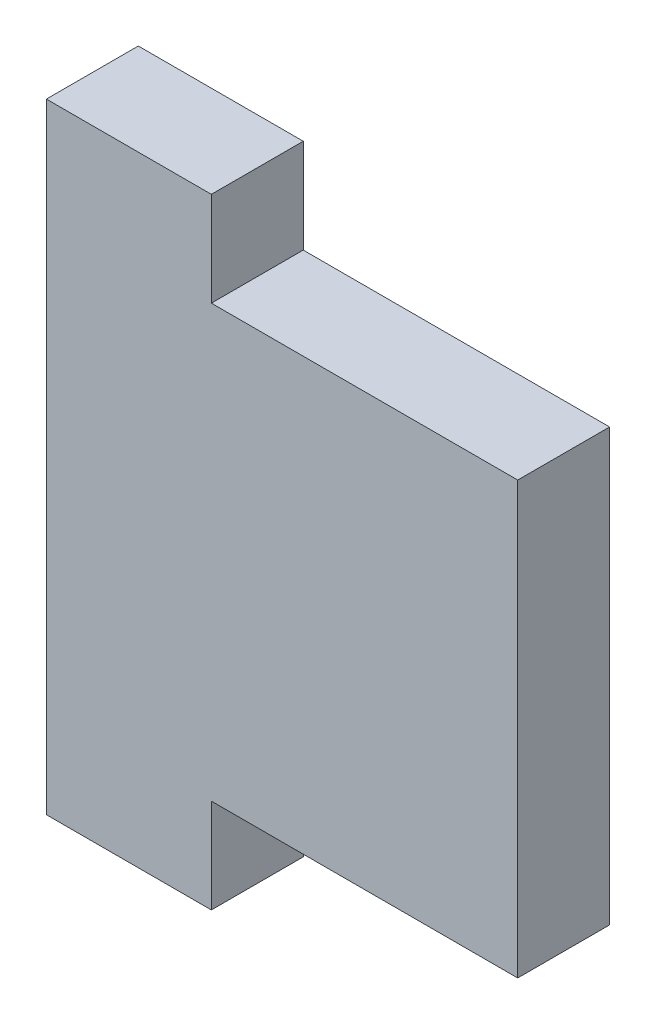
SolidWorks part; units mm, degrees
ref_plane "Front" through (0, 0, 0) normal (0, 0, 1) x (1, 0, 0)
ref_plane "Top" through (0, 0, 0) normal (0, 1, 0) x (1, 0, 0)
ref_plane "Right" through (0, 0, 0) normal (1, 0, 0) x (0, 0, -1)
ref_axis "side-side" through (80.9, 0, 0) along (-1, 0, 0)
ref_axis "up-down" through (0, 50, 0) along (0, -1, 0)
ref_axis "front-back" through (0, 0, -80.9) along (0, 0, 1)
sketch "Sketch1" plane through (0, 0, 0) normal (0, 0, 1) x (1, 0, 0)
  line L0 (-50.038, -11.6205) -> (-84.9201, -11.6205) construction
  line L1 (-54.483, 11.6205) -> (-70.993, 11.6205)
  line L2 (-54.483, 11.6205) -> (-54.483, -11.6205)
  line L3 (-54.483, -11.6205) -> (-70.993, -11.6205)
  line L4 (-79.883, 16.7005) -> (-79.883, -16.7005)
  line L5 (-50.038, 11.6205) -> (-84.9201, 11.6205) construction
  line L6 (-54.483, -11.6205) -> (-54.483, 11.6205) construction
  line L7 (-70.993, -11.6205) -> (-70.993, -16.7005)
  line L8 (-70.993, 16.7005) -> (-79.883, 16.7005)
  line L9 (-70.993, 16.7005) -> (-70.993, 11.6205)
  line L10 (-70.993, -16.7005) -> (-79.883, -16.7005)
  dimension "D1" = 25.4
  dimension "D2" = 8.89
  dimension "D3" = 5.08
  dimension "D4" = 5.08
extrude "Boss-Extrude1" add sketch "Sketch1" along normal mid plane 4.953
